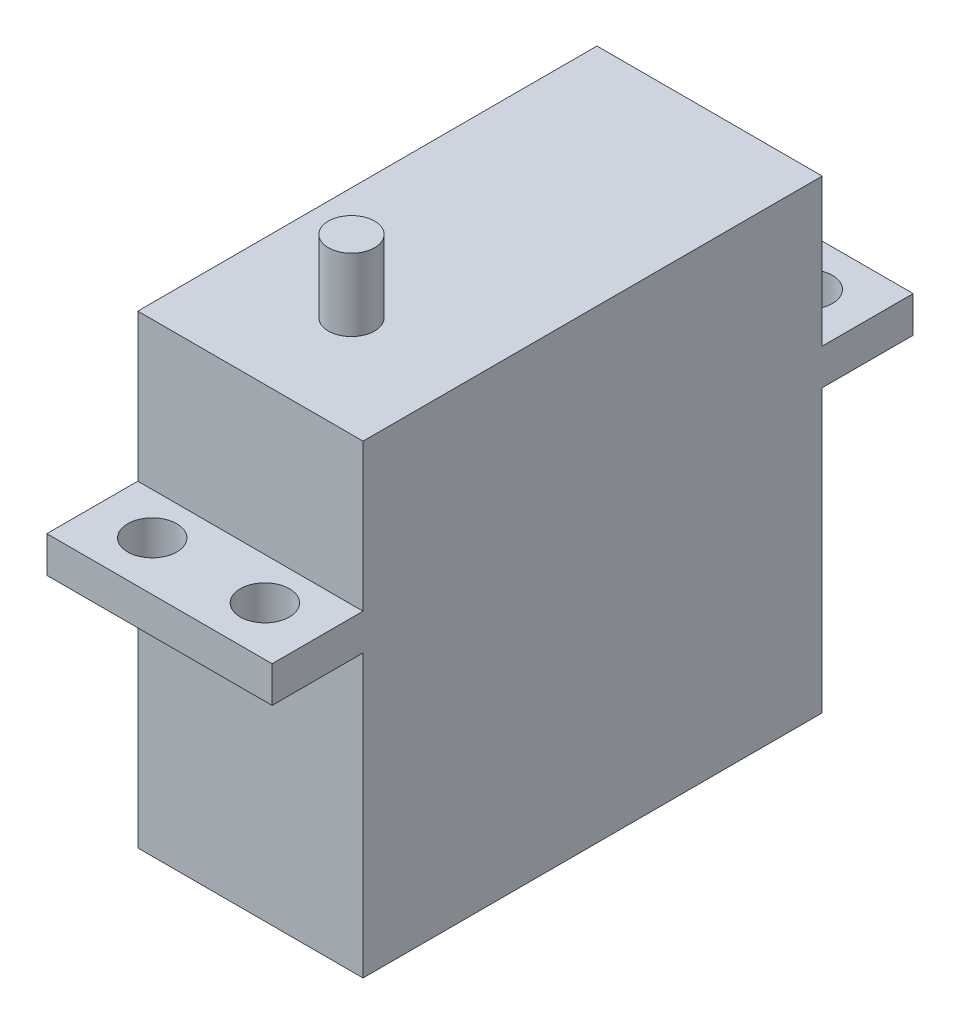
SolidWorks part; units mm, degrees
ref_plane "Front Plane" through (0, 0, 0) normal (0, 0, 1) x (1, 0, 0)
ref_plane "Top Plane" through (0, 0, 0) normal (0, 1, 0) x (1, 0, 0)
ref_plane "Right Plane" through (0, 0, 0) normal (1, 0, 0) x (0, 0, -1)
sketch "Sketch1" plane through (0, 0, 0) normal (1, 0, 0) x (0, 0, -1)
  line L1 (-20.193, 20.447) -> (20.193, 20.447)
  line L2 (-20.193, 20.447) -> (-20.193, -20.447)
  line L3 (-20.193, -20.447) -> (20.193, -20.447)
  line L4 (20.193, 20.447) -> (20.193, -20.447)
  line L5 (-20.193, 20.447) -> (20.193, -20.447) construction
  line L6 (-20.193, -20.447) -> (20.193, 20.447) construction
  point P0 (0, 0)
  dimension "D1" = 40.386
  dimension "D2" = 40.894
extrude "Boss-Extrude1" add sketch "Sketch1" along normal mid plane 19.812
sketch "Sketch2" plane through (9.906, 0, 0) normal (1, 0, 0) x (0, 0, -1)
  line L0 (0, 10.8966) -> (0, -10.8966) construction
  line L1 (-28.194, 4.318) -> (28.194, 4.318)
  line L2 (-28.194, 4.318) -> (-28.194, 7.493)
  line L3 (-28.194, 7.493) -> (28.194, 7.493)
  line L4 (28.194, 4.318) -> (28.194, 7.493)
  line L5 (-28.194, 4.318) -> (28.194, 7.493) construction
  line L6 (-28.194, 7.493) -> (28.194, 4.318) construction
  line L7 (-20.193, -20.447) -> (20.193, -20.447) construction
  point P0 (0, 5.9055)
  dimension "D1" = 27.94
  dimension "D2" = 3.175
  dimension "D3" = 56.388
extrude "Boss-Extrude2" add sketch "Sketch2" against normal through all
sketch "Sketch3" plane through (0, 7.493, 0) normal (0, 1, 0) x (1, 0, 0)
  line L1 (-4.953, 23.876) -> (4.953, 23.876) construction
  line L2 (-4.953, 23.876) -> (-4.953, -23.876) construction
  line L3 (-4.953, -23.876) -> (4.953, -23.876) construction
  line L4 (4.953, 23.876) -> (4.953, -23.876) construction
  line L5 (-4.953, 23.876) -> (4.953, -23.876) construction
  line L6 (-4.953, -23.876) -> (4.953, 23.876) construction
  circle A0 centre (-4.953, 23.876) radius 2.159
  circle A1 centre (4.953, 23.876) radius 2.159
  circle A2 centre (4.953, -23.876) radius 2.159
  circle A3 centre (-4.953, -23.876) radius 2.159
  point P0 (0, 0)
  dimension "D1" = 9.906
  dimension "D3" = 4.318
  dimension "D2" = 47.752
extrude "Cut-Extrude1" cut sketch "Sketch3" against normal blind 19.812
sketch "Sketch4" plane through (0, 20.447, 0) normal (0, 1, 0) x (1, 0, 0)
  line L0 (0, -22.4917) -> (0, 22.4917) construction
  line L1 (9.906, -20.193) -> (-9.906, -20.193) construction
  circle A0 centre (0, -11.303) radius 2.032
  dimension "D1" = 8.89
  dimension "D2" = 4.064
extrude "Boss-Extrude3" add sketch "Sketch4" along normal blind 6.35
ref_axis "Axis1" through (0, 26.797, 11.303) along (0, -1, 0)
